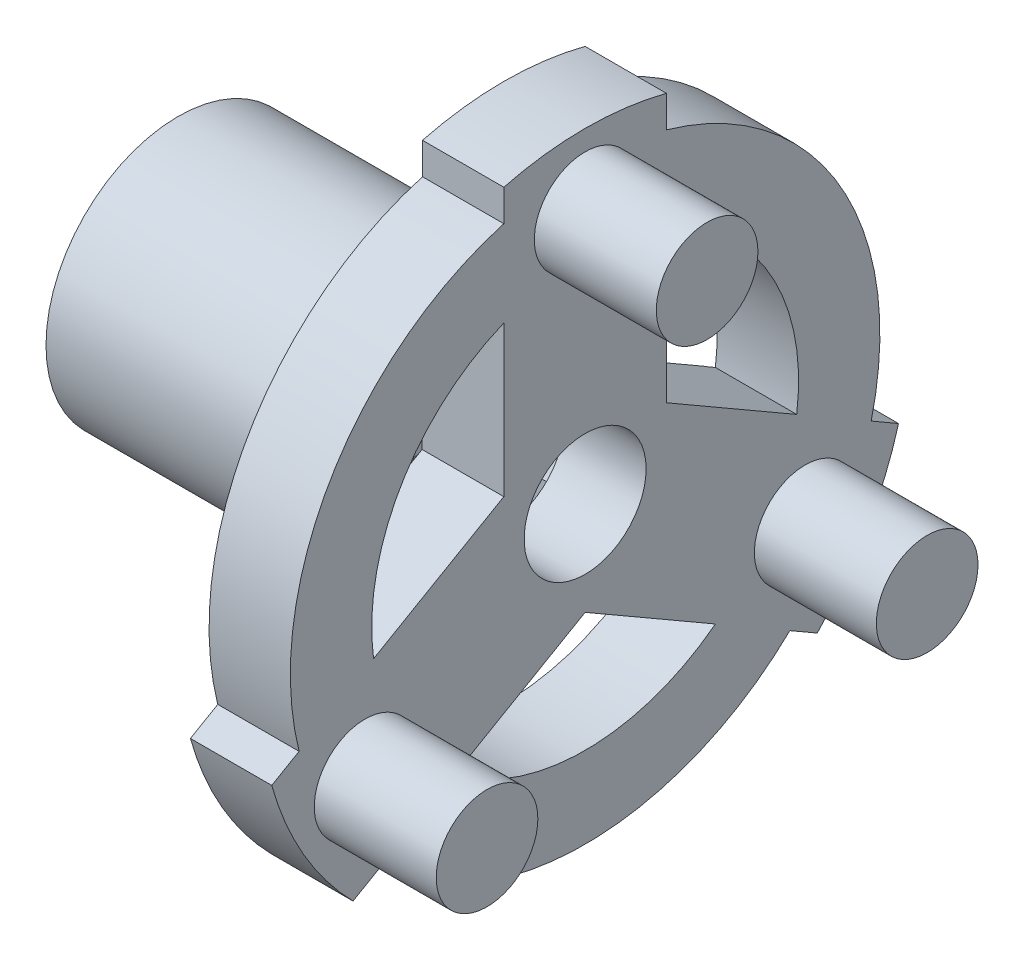
SolidWorks part; units mm, degrees
ref_plane "前视基准面" through (0, 0, 0) normal (0, 0, 1) x (1, 0, 0)
ref_plane "上视基准面" through (0, 0, 0) normal (0, 1, 0) x (1, 0, 0)
ref_plane "右视基准面" through (0, 0, 0) normal (1, 0, 0) x (0, 0, -1)
other "Configuration Table"
sketch "草图1" plane through (0, 0, 0) normal (1, 0, 0) x (0, 0, -1)
  circle A0 centre (0, 0) radius 8
  circle A1 centre (0, 6.25) radius 1.25
  circle A2 centre (5.4127, -3.125) radius 1.25
  circle A3 centre (-5.4127, -3.125) radius 1.25
  point P12 (0, 0)
  dimension "D2" = 2.5
  dimension "D3" = 16
  dimension "D1" = 6.25
  dimension "D4" = 3
extrude "凸台-拉伸1" add sketch "草图1" along normal blind 2 contours A0
extrude "凸台-拉伸2" add sketch "草图1<3>" along normal blind 3 from surface contours A1 | A3 | A2 region at (0, 6.25, 0) region at (0, -3.125, -5.4127) region at (0, -3.125, 5.4127) starting at face at (2, 0, -8)
sketch "草图1<3>" plane through (0, 0, 0) normal (1, 0, 0) x (0, 0, -1) same geometry as "草图1"
sketch "草图2" plane through (0, 0, 0) normal (-1, 0, 0) x (0, 0, 1)
  circle A0 centre (0, 0) radius 1.5
  circle A1 centre (0, 0) radius 5
  dimension "D1" = 3
  dimension "D2" = 10
extrude "凸台-拉伸3" add sketch "草图2" along normal blind 0.01
sketch "草图3" plane through (-0.01, 0, 0) normal (-1, 0, 0) x (0, 0, 1)
  line L1 (-2.1928, -1.0928) -> (2.1928, -1.0928)
  line L2 (-2.1928, -1.0928) -> (-2.1928, 1.0928)
  line L3 (-2.1928, 1.0928) -> (2.1928, 1.0928)
  line L4 (2.1928, -1.0928) -> (2.1928, 1.0928)
  line L5 (-2.1928, -1.0928) -> (2.1928, 1.0928) construction
  line L6 (-2.1928, 1.0928) -> (2.1928, -1.0928) construction
  line L7 (-1.0928, -2.1928) -> (1.0928, -2.1928)
  line L8 (-1.0928, -2.1928) -> (-1.0928, 2.1928)
  line L9 (-1.0928, 2.1928) -> (1.0928, 2.1928)
  line L10 (1.0928, -2.1928) -> (1.0928, 2.1928)
  line L11 (-1.0928, -2.1928) -> (1.0928, 2.1928) construction
  line L12 (-1.0928, 2.1928) -> (1.0928, -2.1928) construction
  circle A0 centre (0, 0) radius 2.45
  circle A1 centre (0, 0) radius 3.25
  dimension "D1" = 6.5
  dimension "D2" = 4.9
  dimension "D3" = 1.1
extrude "凸台-拉伸4" add sketch "草图3" along normal blind 8 contours A1 A0 | L8 A0 L3 | L1 A0 L8 | L10 A0 L1 | L3 A0 L10 region at (-0.01, -1.4988, -1.4988) region at (-0.01, 1.4988, -1.4988) region at (-0.01, -1.4988, 1.4988) region at (-0.01, 1.4988, 1.4988) region at (-0.01, 0, -3.1581)
extrude "切除-拉伸1" cut sketch "草图2<2>" against normal through all both and the other way through all contours A0 region at (0, 0, 0)
sketch "草图2<2>" plane through (0, 0, 0) normal (-1, 0, 0) x (0, 0, 1) same geometry as "草图2"
sketch "草图4" plane through (2, 0, 0) normal (1, 0, 0) x (0, 0, -1)
  line L0 (7.7082, -2.1409) -> (1, 1.7321)
  line L1 (-2, 7.746) -> (2, 7.746)
  line L2 (-2, 7.746) -> (-2, 0)
  line L3 (-2, 0) -> (2, 0)
  line L4 (2, 7.746) -> (2, 0)
  line L5 (7.7082, -2.1409) -> (5.7082, -5.605)
  line L6 (5.7082, -5.605) -> (-1, -1.7321)
  line L7 (1, 1.7321) -> (-1, -1.7321)
  line L8 (-5.7082, -5.605) -> (1, -1.7321)
  line L9 (-5.7082, -5.605) -> (-7.7082, -2.1409)
  line L10 (-7.7082, -2.1409) -> (-1, 1.7321)
  line L11 (1, -1.7321) -> (-1, 1.7321)
  circle A0 centre (0, 0) radius 8 construction
  circle A2 centre (0, 0) radius 5.25
  circle A3 centre (0, 0) radius 7.25
  circle A4 centre (0, 0) radius 8
  point P19 (0, 0)
  dimension "D2" = 10.5
  dimension "D3" = 14.5
  dimension "D4" = 16
  dimension "D5" = 4
  dimension "D1" = 3
extrude "切除-拉伸2" cut sketch "草图4" against normal up to surface (2.01 mm away) contours L2 A2 L10 | L0 A2 L4 | L8 A2 L6 | L2 A4 L10 A3 | L0 A4 L4 A3 | L8 A4 L6 A3 region at (2, -1.8465, -7.4295) region at (2, -7.8825, 0) region at (2, 2.0069, -3.476) region at (2, -4.0137, 0) region at (2, 3.9422, 6.828) region at (2, 2.0069, 3.476) up to face at (-0.01, 0, 3.25)
